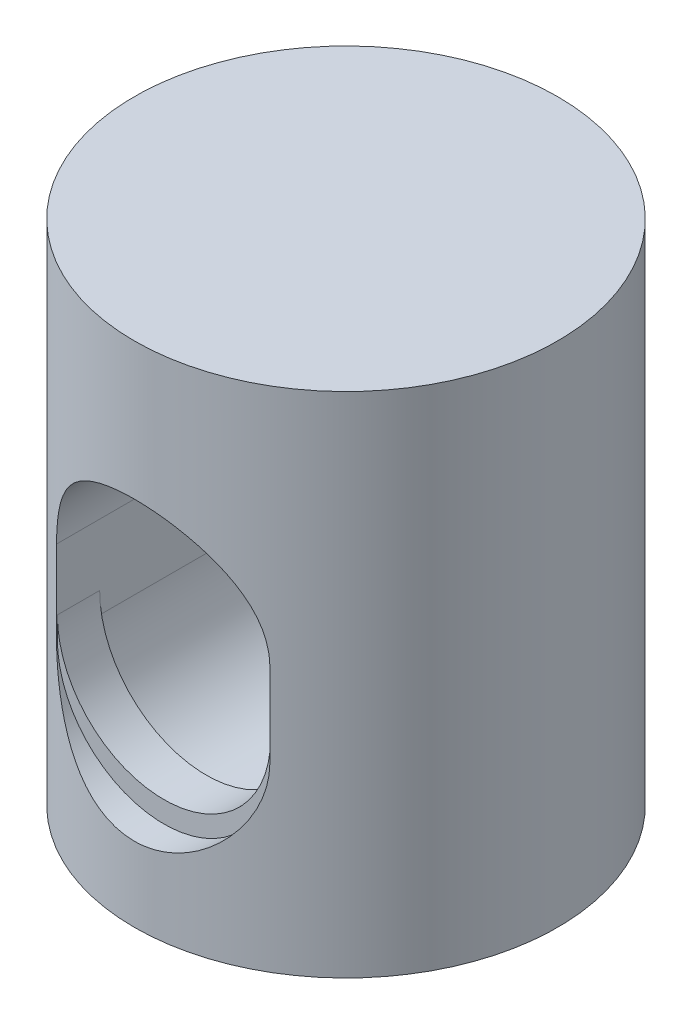
SolidWorks part; units mm, degrees
material "Alloy Steel"
ref_plane "Front Plane" through (0, 0, 0) normal (0, 0, 1) x (1, 0, 0)
ref_plane "Top Plane" through (0, 0, 0) normal (0, 1, 0) x (1, 0, 0)
ref_plane "Right Plane" through (0, 0, 0) normal (1, 0, 0) x (0, 0, -1)
sketch "Sketch2" plane through (0, 0, 0) normal (0, 1, 0) x (1, 0, 0)
  circle A0 centre (0, 0) radius 6.35
  dimension "D1" = 12.7
extrude "Boss-Extrude1" add sketch "Sketch2" along normal blind 15.24
ref_plane "Plane1" through (0, 0, 6.35) normal (0, 0, 1) x (1, 0, 0)
sketch "Sketch4" plane through (0, 0, 6.35) normal (0, 0, 1) x (1, 0, 0)
  line L0 (0, 0) -> (0, 15.24) construction
  line L1 (6.35, 15.24) -> (-6.35, 15.24) construction
  line L2 (0, 5.4408) -> (0, 7.93) construction
  line L3 (-3.2004, 5.4408) -> (-3.2004, 7.93)
  line L4 (3.2004, 5.4408) -> (3.2004, 7.93)
  arc A0 (-3.2004, 5.4408) -> (3.2004, 5.4408) centre (0, 5.4408) ccw
  arc A1 (3.2004, 7.93) -> (-3.2004, 7.93) centre (0, 7.93) ccw
  circle A2 centre (0, 6.0758) radius 3.2004
  point P7 (0, 6.6854)
  point P12 (0, 11.1304)
  point P13 (0, 2.2404)
  point P16 (0, 8.6177)
  point P17 (0, 8.5605)
  point P18 (0, 0)
  point P19 (0, 0)
  point P20 (0, 0)
  point P21 (0, 8.3989)
  point P22 (0, 7.93)
  point P23 (0, 6.2829)
  dimension "D3" = 0.635
  dimension "D1" = 6.4008
  dimension "D2" = 8.89
extrude "Cut-Extrude1" cut sketch "Sketch4" against normal blind 0.889 contours A0 L4 A1 L3
extrude "Cut-Extrude2" cut sketch "Sketch4<3>" against normal up to next contours A1 A2 region at (0, 6.0758, 6.35)
sketch "Sketch4<3>" plane through (0, 0, 6.35) normal (0, 0, 1) x (1, 0, 0) same geometry as "Sketch4"
extrude "Cut-Extrude3" cut sketch "Sketch4<4>" against normal up to next contours A2 L4 A1 L3 region at (0, 9.5164, 6.35)
sketch "Sketch4<4>" plane through (0, 0, 6.35) normal (0, 0, 1) x (1, 0, 0) same geometry as "Sketch4"
ref_plane "Plane2" through (0, 0, 4.191) normal (0, 0, 1) x (1, 0, 0)
extrude "Cut-Extrude4" cut sketch "Sketch4<5>" against normal up to next from surface contours A0 L4 A1 L3 starting at plane "Plane2"
sketch "Sketch4<5>" plane through (0, 0, 6.35) normal (0, 0, 1) x (1, 0, 0) same geometry as "Sketch4"
